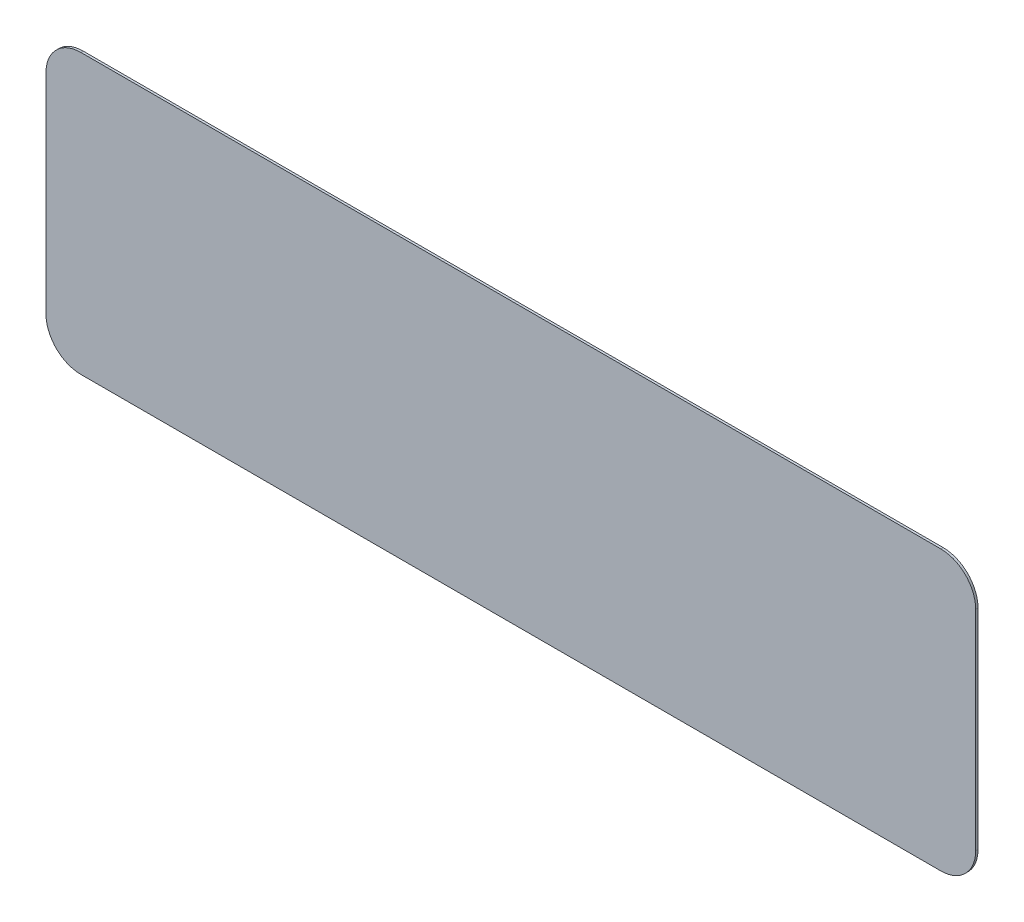
SolidWorks part; units mm, degrees
ref_plane "Front Plane" through (0, 0, 0) normal (0, 0, 1) x (1, 0, 0)
ref_plane "Top Plane" through (0, 0, 0) normal (0, 1, 0) x (1, 0, 0)
ref_plane "Right Plane" through (0, 0, 0) normal (1, 0, 0) x (0, 0, -1)
ref_axis "Axis1" through (0, 0, 0) along (0, 1, 0)
sketch "Sketch1" plane through (0, 0, 0) normal (0, 0, 1) x (1, 0, 0)
  line L1 (-18.5, 0) -> (18.5, 0)
  line L2 (-20, 1.5) -> (-20, 10.5)
  line L3 (-18.5, 12) -> (18.5, 12)
  line L4 (20, 1.5) -> (20, 10.5)
  arc A0 (18.5, 12) -> (20, 10.5) centre (18.5, 10.5) cw
  arc A1 (18.5, 0) -> (20, 1.5) centre (18.5, 1.5) ccw
  arc A2 (-18.5, 0) -> (-20, 1.5) centre (-18.5, 1.5) cw
  arc A3 (-20, 10.5) -> (-18.5, 12) centre (-18.5, 10.5) cw
  point P7 (20, 12)
  point P10 (20, 0)
  point P13 (-20, 0)
  dimension "D3" = 1.5
  dimension "D1" = 40
  dimension "D2" = 12
extrude "Boss-Extrude1" add sketch "Sketch1" along normal blind 0.1
